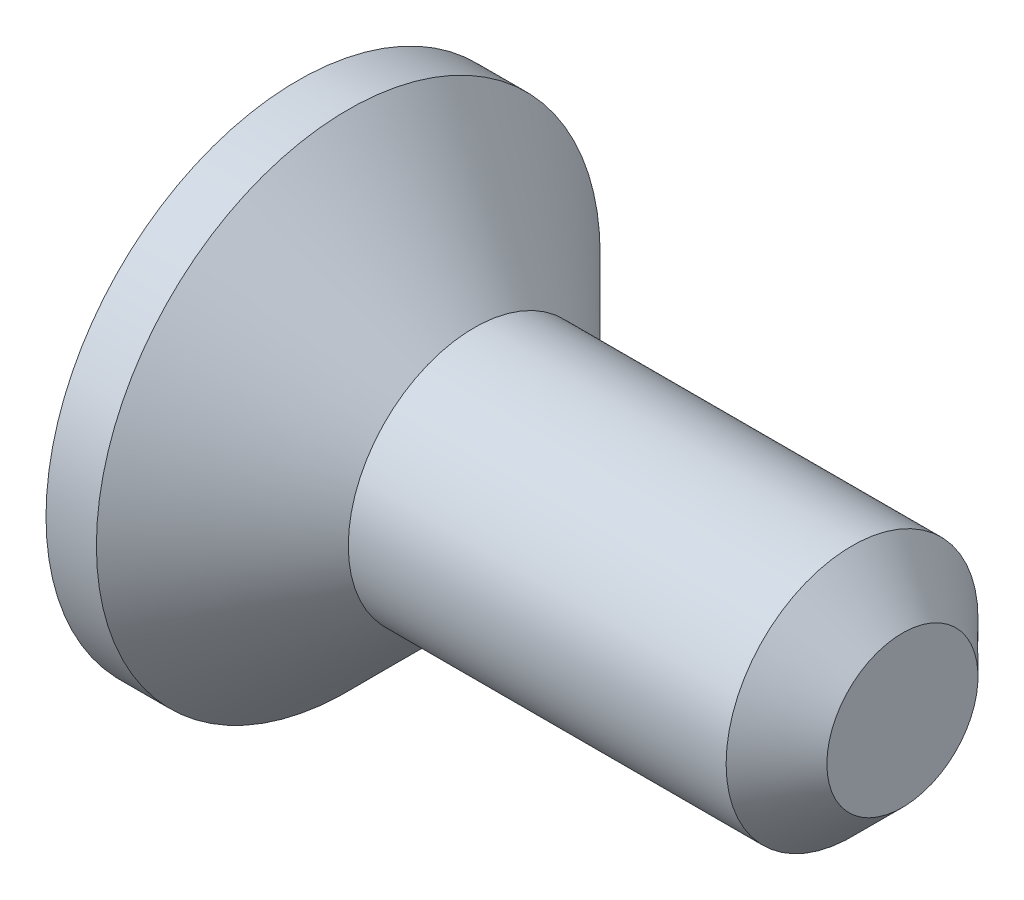
SolidWorks part; units mm, degrees
ref_plane "Front Plane" through (0, 0, 0) normal (0, 0, 1) x (1, 0, 0)
ref_plane "Top Plane" through (0, 0, 0) normal (0, 1, 0) x (1, 0, 0)
ref_plane "Right Plane" through (0, 0, 0) normal (1, 0, 0) x (0, 0, -1)
sketch "Sketch2" plane through (0, 0, 0) normal (0, 0, 1) x (1, 0, 0)
  line L0 (0, 0) -> (0, 2.5)
  line L1 (0, 2.5) -> (0.5, 2.5)
  line L2 (0.5, 2.5) -> (1.75, 1.25)
  line L3 (1.75, 1.25) -> (5.5, 1.25)
  line L4 (5.5, 1.25) -> (6, 0.75)
  line L5 (6, 0.75) -> (6, 0)
  line L6 (6, 0) -> (0, 0)
  line L7 (-2.2818, 0) -> (8.0811, 0) construction
  line L8 (1.75, 1.25) -> (0, 1.25) construction
  dimension "D1" = 5
  dimension "D2" = 0.5
  dimension "D3" = 45
  dimension "D4" = 6
  dimension "D5" = 0.5
revolve "Revolve1" add sketch "Sketch2" angle 360 about L7
sketch "Sketch3" plane through (0, 0, 0) normal (-1, 0, 0) x (0, 0, 1)
  line L1 (0.433, -0.75) -> (0.866, 0)
  line L2 (0.866, 0) -> (0.433, 0.75)
  line L3 (0.433, 0.75) -> (-0.433, 0.75)
  line L4 (-0.433, 0.75) -> (-0.866, 0)
  line L5 (-0.866, 0) -> (-0.433, -0.75)
  line L6 (-0.433, -0.75) -> (0.433, -0.75)
  circle A0 centre (0, 0) radius 0.75 construction
  dimension "D1" = 1.5
extrude "Cut-Extrude1" cut sketch "Sketch3" against normal blind 0.8
